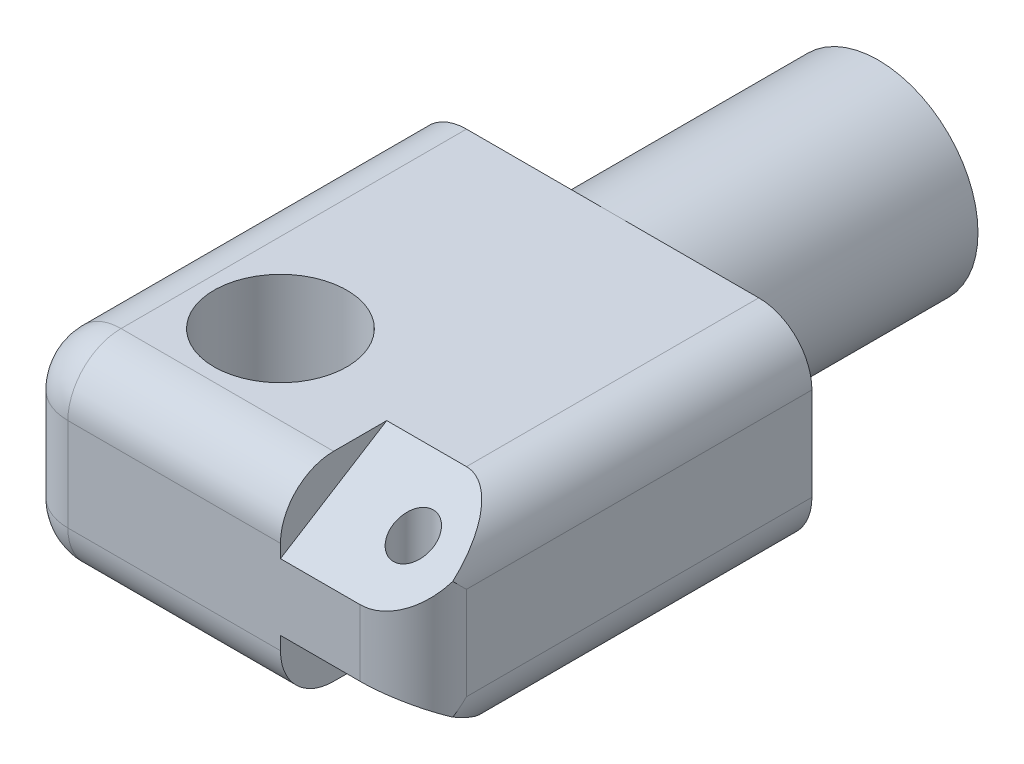
SolidWorks part; units mm, degrees
ref_plane "Front Plane" through (0, 0, 0) normal (0, 0, 1) x (1, 0, 0)
ref_plane "Top Plane" through (0, 0, 0) normal (0, 1, 0) x (1, 0, 0)
ref_plane "Right Plane" through (0, 0, 0) normal (1, 0, 0) x (0, 0, -1)
sketch "Sketch1" plane through (0, 0, 0) normal (0, 1, 0) x (1, 0, 0)
  line L0 (-5, -5) -> (10, -5)
  line L1 (10, -5) -> (10, 10)
  line L2 (10, 10) -> (-5, 10)
  line L3 (-5, 10) -> (-5, -5)
  circle A0 centre (0, 0) radius 2.5
  dimension "D1" = 5
  dimension "D3" = 5
  dimension "D2" = 5
  dimension "D4" = 15
  dimension "D5" = 15
extrude "Boss-Extrude1" add sketch "Sketch1" along normal blind 7.5
sketch "Sketch2" plane through (0, 0, -10) normal (0, 0, -1) x (-1, 0, 0)
  line L0 (-10, 0) -> (5, 0) construction
  line L1 (5, 7.5) -> (5, 0) construction
  circle A0 centre (-2.5, 3.75) radius 3.75
  dimension "D1" = 7.5
  dimension "D2" = 3.75
  dimension "D3" = 7.5
extrude "Boss-Extrude2" add sketch "Sketch2" along normal blind 10
sketch "Sketch3" plane through (0, 7.5, 0) normal (0, 1, 0) x (1, 0, 0)
  line L0 (-5, -5) -> (10, -5) construction
  line L1 (10, -5) -> (10, 10) construction
  circle A0 centre (8, -3) radius 0.75
  dimension "D1" = 1.5
  dimension "D2" = 2
  dimension "D3" = 2
extrude "Cut-Extrude1" cut sketch "Sketch3" against normal blind 7.5
sketch "Sketch4" plane through (10, 0, 0) normal (1, 0, 0) x (0, 0, -1)
  line L0 (-5, 7.5) -> (-1, 7.5)
  line L1 (-5, 7.5) -> (10, 7.5) construction
  line L2 (-1, 7.5) -> (-5, 5)
  line L3 (-5, 7.5) -> (-5, 0) construction
  line L4 (-5, 5) -> (-5, 7.5)
  line L5 (-5, 0) -> (-1, 0)
  line L6 (-5, 0) -> (10, 0) construction
  line L7 (-1, 0) -> (-5, 2.5)
  line L8 (-5, 2.5) -> (-5, 0)
  dimension "D1" = 2.5
  dimension "D2" = 2.5
  dimension "D3" = 4
  dimension "D4" = 4
extrude "Cut-Extrude2" cut sketch "Sketch4" against normal blind 5
fillet "Fillet1" radius 2 8 edges at (10, 3.75, 5) (-5, 3.75, 5) (-5, 0, -2.5) (-5, 7.5, -2.5) (0, 0, 5) (10, 0, -4.5) (10, 7.5, -4.5) (0, 7.5, 5)
